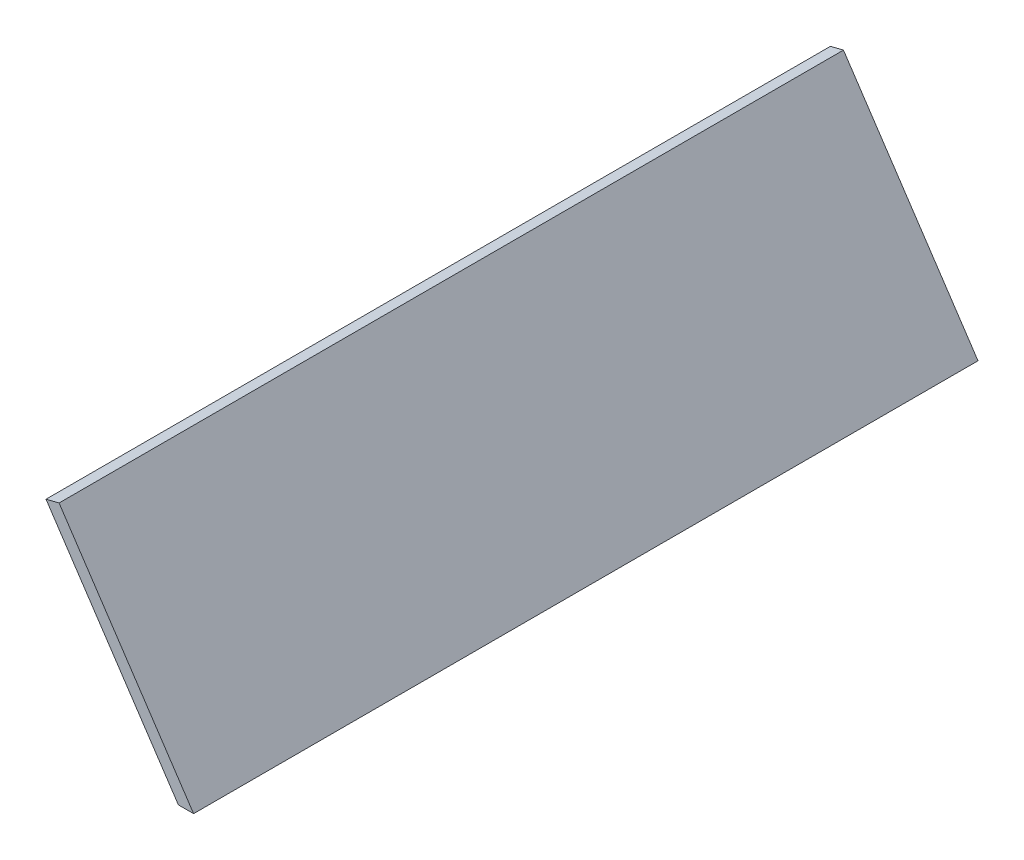
SolidWorks part; units mm, degrees
material "5052-H34"
ref_plane "Front Plane" through (0, 0, 0) normal (0, 0, 1) x (1, 0, 0)
ref_plane "Top Plane" through (0, 0, 0) normal (0, 1, 0) x (1, 0, 0)
ref_plane "Right Plane" through (0, 0, 0) normal (1, 0, 0) x (0, 0, -1)
sketch "Sketch1" plane through (0, 0, 0) normal (0, 0, 1) x (1, 0, 0)
  line L6 (-194.8923, -15.5826) -> (-148.0708, -85.8151)
  line L7 (-148.0708, -85.8151) -> (-142.6803, -85.8151)
  line L8 (-194.8923, -15.5826) -> (-190.2721, -14.4272)
  line L9 (-190.2721, -14.4272) -> (-142.6803, -85.8151)
  line L10 (-142.6803, -85.8151) -> (-125.3132, -85.8151)
  dimension "D1" = 123.69
  dimension "D2" = 123.69
  dimension "D3" = 4.7625
  dimension "D4" = 70.35
  dimension "D5" = 70.2325
extrude "Boss-Extrude1" add sketch "Sketch1" along normal blind 277.48 contours L6 L7 L9 L8
